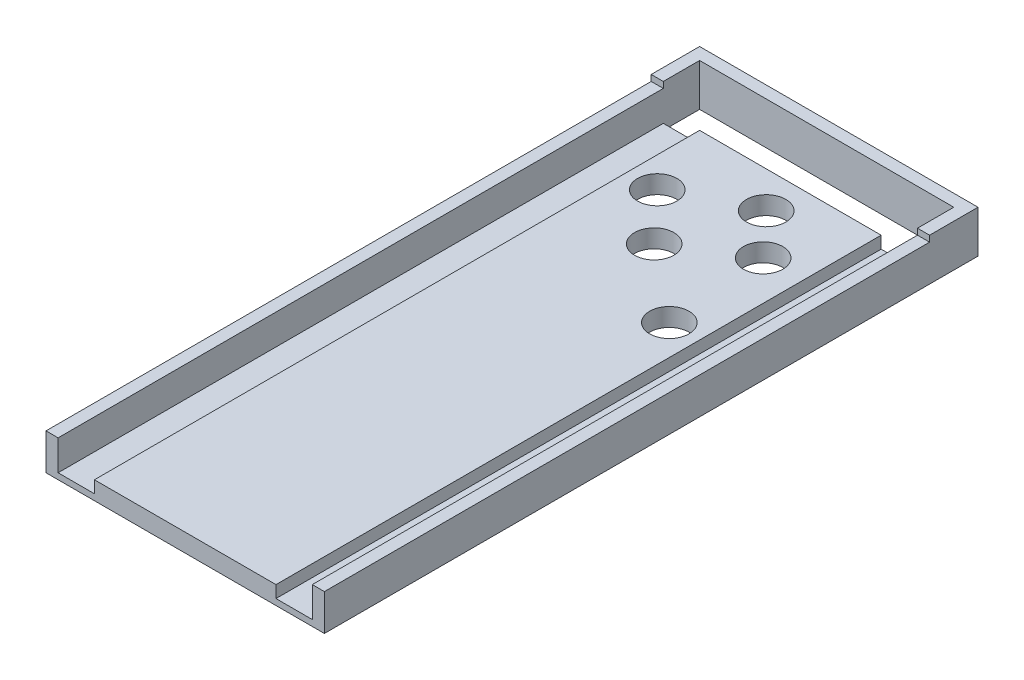
SolidWorks part; units mm, degrees
ref_plane "Front Plane" through (0, 0, 0) normal (0, 0, 1) x (1, 0, 0)
ref_plane "Top Plane" through (0, 0, 0) normal (0, 1, 0) x (1, 0, 0)
ref_plane "Right Plane" through (0, 0, 0) normal (1, 0, 0) x (0, 0, -1)
sketch "Sketch1" plane through (0, 0, 0) normal (0, 1, 0) x (1, 0, 0)
  line L1 (0, 0) -> (0.3, 0)
  line L2 (0, 0) -> (0, 1)
  line L3 (0, 1) -> (0.3, 1)
  line L4 (0.3, 0) -> (0.3, 1)
  line L5 (0, 0) -> (-0.06, 0)
  line L6 (0, 0) -> (0, 1)
  line L7 (0, 1) -> (-0.06, 1)
  line L8 (-0.06, 0) -> (-0.06, 1)
  line L9 (0.3, 0) -> (0.36, 0)
  line L10 (0.3, 0) -> (0.3, 1)
  line L11 (0.3, 1) -> (0.36, 1)
  line L12 (0.36, 0) -> (0.36, 1)
  line L13 (-0.06, 0) -> (-0.08, 0)
  line L14 (-0.06, 0) -> (-0.06, 1)
  line L15 (-0.06, 1) -> (-0.08, 1)
  line L16 (-0.08, 0) -> (-0.08, 1)
  line L17 (0.36, 0) -> (0.38, 0)
  line L18 (0.36, 0) -> (0.36, 1)
  line L19 (0.36, 1) -> (0.38, 1)
  line L20 (0.38, 0) -> (0.38, 1)
  dimension "D1" = 1
  dimension "D2" = 0.3
  dimension "D3" = 0.06
  dimension "D4" = 0.02
extrude "Boss-Extrude2" add sketch "Sketch1" along normal blind 0.03 contours L1 L4 L3 L2 region at (0.15, 0, -0.5)
extrude "Boss-Extrude3" add sketch "Sketch1<6>" along normal blind 0.01 contours L8 L5 L2 L7 | L9 L12 L11 L4 region at (-0.03, 0, -0.5) region at (0.33, 0, -0.5)
sketch "Sketch1<6>" plane through (0, 0, 0) normal (0, 1, 0) x (1, 0, 0) same geometry as "Sketch1"
extrude "Boss-Extrude4" add sketch "Sketch1<7>" along normal blind 0.06 contours L16 L13 L8 L15 | L17 L20 L19 L12 region at (-0.07, 0, -0.5) region at (0.37, 0, -0.5)
sketch "Sketch1<7>" plane through (0, 0, 0) normal (0, 1, 0) x (1, 0, 0) same geometry as "Sketch1"
sketch "Sketch3" plane through (0, 0, 0) normal (0, 1, 0) x (1, 0, 0)
  line L0 (0.38, 0) -> (0.38, 1) construction
  line L1 (-0.08, 1) -> (0.38, 1)
  line L2 (-0.08, 1) -> (-0.08, 1.08)
  line L3 (-0.08, 1.08) -> (0.38, 1.08)
  line L4 (0.38, 1) -> (0.38, 1.08)
  dimension "D1" = 0.08
extrude "Boss-Extrude7" add sketch "Sketch3" along normal blind 0.07
sketch "Sketch6" plane through (0, 0.07, 0) normal (0, 1, 0) x (1, 0, 0)
  line L0 (0.36, 0) -> (0.36, 1) construction
  line L1 (-0.06, 1) -> (0.36, 1)
  line L2 (-0.06, 1) -> (-0.06, 1.06)
  line L3 (-0.06, 1.06) -> (0.36, 1.06)
  line L4 (0.36, 1) -> (0.36, 1.06)
  line L5 (0.38, 1.08) -> (-0.08, 1.08) construction
  dimension "D1" = 0.02
extrude "Cut-Extrude1" cut sketch "Sketch6" against normal up to next
sketch "Sketch7" plane through (0, 0.03, 0) normal (0, 1, 0) x (1, 0, 0)
  line L0 (0, 0) -> (0, 1) construction
  line L1 (0, 1) -> (0.3, 1) construction
  line L2 (0.3, 0) -> (0.3, 1) construction
  circle A0 centre (0.05, 0.88) radius 0.0325
  circle A1 centre (0.125, 0.8) radius 0.0325
  circle A2 centre (0.235, 0.87) radius 0.0325
  circle A3 centre (0.17, 0.94) radius 0.0325
  circle A4 centre (0.25, 0.7) radius 0.0325
  dimension "D1" = 0.065
  dimension "D2" = 0.05
  dimension "D3" = 0.12
  dimension "D4" = 0.06
  dimension "D5" = 0.13
  dimension "D6" = 0.13
  dimension "D7" = 0.065
  dimension "D8" = 0.2
  dimension "D9" = 0.125
  dimension "D10" = 0.3
  dimension "D11" = 0.05
extrude "Cut-Extrude2" cut sketch "Sketch7" against normal up to next
